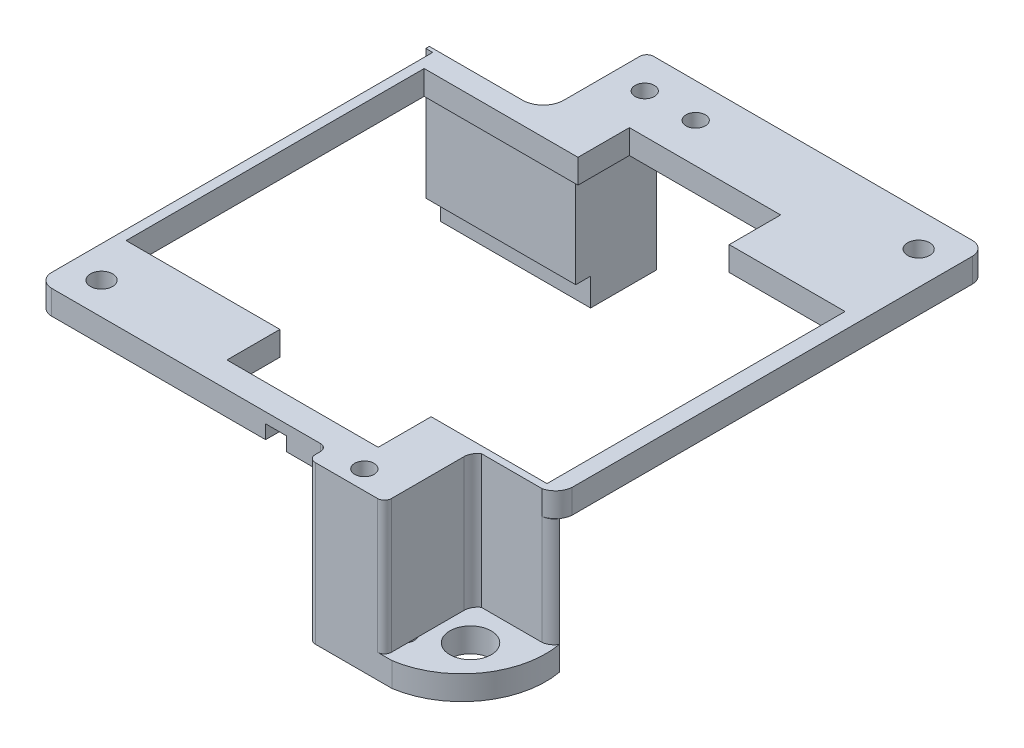
SolidWorks part; units mm, degrees
ref_plane "Спереди" through (0, 0, 0) normal (0, 0, 1) x (1, 0, 0)
ref_plane "Сверху" through (0, 0, 0) normal (0, 1, 0) x (1, 0, 0)
ref_plane "Справа" through (0, 0, 0) normal (1, 0, 0) x (0, 0, -1)
sketch "Sketch2" plane through (0, 3.6, 0) normal (0, -1, 0) x (1, 0, 0)
  line L22 (11.1116, -27.048) -> (11.1116, -19.6)
  line L23 (11.1116, -19.6) -> (27.9, -19.6)
  line L24 (27.9, -19.6) -> (27.9, 23.6)
  line L25 (27.9, 23.6) -> (11.1116, 23.6)
  line L26 (11.1116, 23.6) -> (11.1116, 31.2769)
  line L27 (11.1116, 31.2769) -> (1.5, 31.2769)
  line L28 (1.5, 31.2769) -> (1.5, 34.9854)
  line L29 (1.5, 34.9854) -> (6.4639, 34.9854)
  line L30 (-1.5, 31.2769) -> (-10.8084, 31.2769)
  line L31 (-10.8084, 31.2769) -> (-10.8084, 23.6)
  line L32 (-10.8084, 23.6) -> (-33.1, 23.6)
  line L33 (-33.5, -27.6627) -> (-33.5, -23.75)
  line L34 (-32.5, -22.75) -> (-22, -22.75)
  line L35 (-19, -25.75) -> (-19, -36.75)
  line L36 (-18, -37.75) -> (28.1923, -37.75)
  line L37 (30.1923, -35.7501) -> (30.1923, 22.25)
  line L38 (28.1923, 24.5898) -> (19.3848, 24.5898)
  line L39 (18.5, 26.25) -> (18.5, 36.75)
  line L40 (17.5, 37.75) -> (8.4639, 37.75)
  line L41 (7.4639, 36.75) -> (7.4639, 35.9854)
  line L42 (-1.5, 34.9854) -> (-32.5, 34.9854)
  line L43 (-34.5, 32.9854) -> (-34.5, -28.6627)
  line L44 (-33.1, 23.6) -> (-33.1, -19.6)
  line L45 (-33.1, -19.6) -> (-10.8084, -19.6)
  line L46 (-10.8084, -19.6) -> (-10.8084, -27.048)
  line L47 (-10.8084, -27.048) -> (11.1116, -27.048)
  line L48 (-1.5, 31.2769) -> (-1.5, 34.9854)
  circle A0 centre (-6.9188, -32.7663) radius 1.4
  circle A22 centre (25.4, -32.7663) radius 1.6
  circle A23 centre (-14.2971, -32.7663) radius 1.4
  circle A24 centre (-29.9119, 30.3479) radius 1.6
  circle A25 centre (12.8146, 34.9854) radius 1.4
  arc A33 (-34.5, -28.6627) -> (-33.5, -27.6627) centre (-34.5, -27.6627) ccw
  arc A34 (-32.5, -22.75) -> (-33.5, -23.75) centre (-32.5, -23.75) ccw
  arc A35 (-19, -25.75) -> (-22, -22.75) centre (-22, -25.75) ccw
  arc A36 (-19, -36.75) -> (-18, -37.75) centre (-18, -36.75) ccw
  arc A37 (28.1923, -37.75) -> (30.1923, -35.7501) centre (28.1923, -35.75) ccw
  arc A38 (30.1923, 22.25) -> (28.1923, 24.5898) centre (27.5559, 22.0212) ccw
  arc A39 (18.5, 26.25) -> (19.3848, 24.5898) centre (20.5, 26.25) ccw
  arc A40 (18.5, 36.75) -> (17.5, 37.75) centre (17.5, 36.75) ccw
  arc A41 (8.4639, 37.75) -> (7.4639, 36.75) centre (8.4639, 36.75) ccw
  arc A42 (6.4639, 34.9854) -> (7.4639, 35.9854) centre (6.4639, 35.9854) ccw
  arc A43 (-32.5, 34.9854) -> (-34.5, 32.9854) centre (-32.5, 32.9854) ccw
  point P57 (0, 0)
  point P58 (0, 0)
  point P59 (0, 0)
  dimension "D1" = 0
  dimension "D2" = 1.4
extrude "Boss-Extrude1" add sketch "Sketch2" along normal blind 3.5
sketch "Sketch3" plane through (0, 0.1, 0) normal (0, -1, 0) x (-1, 0, 0)
  line L0 (-7.4639, -33.9854) -> (-7.4639, -36.75)
  line L1 (-7.4639, -36.75) -> (-7.4639, -35.9854) construction
  line L2 (-8.4639, -37.75) -> (-17.5, -37.75)
  line L3 (-17.5, -37.75) -> (-8.4639, -37.75) construction
  line L4 (-11.1116, -24.25) -> (-11.1116, -23.6)
  line L5 (-18.5, -36.75) -> (-18.5, -26.25)
  line L6 (-18.5, -26.25) -> (-18.5, -36.75) construction
  line L7 (13.7749, 22.2395) -> (34.5, 22.2395)
  line L8 (-11.1116, -24.25) -> (-11.1116, -33.9854)
  line L9 (-11.1116, -33.9854) -> (-7.4639, -33.9854)
  line L10 (-11.1116, -23.6) -> (-29.6796, -23.6)
  line L12 (-28.1923, -24.5898) -> (-19.3848, -24.5898)
  line L13 (13.7749, 23.7464) -> (13.7749, 22.2395)
  line L14 (29.0773, 22.2395) -> (12.89, 22.2395) construction
  line L15 (34.5, 22.2395) -> (34.5, 23.75)
  line L16 (22, 22.75) -> (32.5, 22.75)
  line L19 (13.7749, 23.7464) -> (13.7749, 31.4673)
  line L20 (13.7749, 31.4673) -> (13.7749, 33.9534)
  line L22 (13.7749, 33.9534) -> (19, 33.9534)
  line L23 (19, 25.75) -> (19, 36.75) construction
  line L24 (19, 33.9534) -> (19, 25.75)
  line L26 (33.5, 27.6627) -> (33.5, 23.75) construction
  line L27 (34.5, -32.9854) -> (34.5, 28.6627) construction
  line L28 (34.5, 23.75) -> (34.5, 28.6627)
  line L30 (33.5, 27.6627) -> (33.5, 23.75)
  arc A0 (-8.4639, -37.75) -> (-7.4639, -36.75) centre (-8.4639, -36.75) ccw construction
  arc A1 (-7.4639, -36.75) -> (-8.4639, -37.75) centre (-8.4639, -36.75) cw
  arc A2 (-18.5, -36.75) -> (-17.5, -37.75) centre (-17.5, -36.75) ccw construction
  arc A3 (-18.5, -26.25) -> (-19.3848, -24.5898) centre (-20.5, -26.25) ccw construction
  arc A4 (-17.5, -37.75) -> (-18.5, -36.75) centre (-17.5, -36.75) cw
  arc A5 (-18.5, -26.25) -> (-19.3848, -24.5898) centre (-20.5, -26.25) ccw
  arc A6 (-30.1923, -22.25) -> (-28.1923, -24.5898) centre (-27.5559, -22.0212) ccw construction
  arc A7 (-29.6796, -23.6) -> (-28.1923, -24.5898) centre (-27.9446, -22.6052) ccw
  arc A8 (19.7672, 23.7464) -> (22, 22.75) centre (22, 25.75) ccw
  arc A9 (33.5, 23.75) -> (32.5, 22.75) centre (32.5, 23.75) cw
  circle A10 centre (-12.8146, -34.9854) radius 1.4
  circle A12 centre (14.2971, 32.7663) radius 1.4 construction
  arc A15 (19, 25.75) -> (22, 22.75) centre (22, 25.75) ccw construction
  arc A16 (19, 25.75) -> (19.7672, 23.7464) centre (22, 25.75) ccw
  arc A17 (32.5, 22.75) -> (33.5, 23.75) centre (32.5, 23.75) ccw construction
  arc A18 (34.5, 28.6627) -> (33.5, 27.6627) centre (34.5, 27.6627) ccw construction
  arc A19 (33.5, 27.6627) -> (34.5, 28.6627) centre (34.5, 27.6627) cw
  point P36 (-19.3848, -24.5898)
extrude "Boss-Extrude2" add sketch "Sketch3" along normal blind 15.8
sketch "Sketch4" plane through (0, -15.7, 0) normal (0, -1, 0) x (1, 0, 0)
  line L0 (11.1116, 23.6) -> (29.6796, 23.6)
  line L1 (-13.7749, -33.9534) -> (-13.7749, -22.2395) construction
  line L2 (-34.5, -22.2395) -> (-34.5, -28.6627) construction
  line L3 (19.5777, 37.75) -> (8.4639, 37.75)
  line L4 (-29.8443, -33.9534) -> (-13.7749, -33.9534)
  line L5 (7.4639, 36.75) -> (7.4639, 33.9854)
  line L6 (7.4639, 33.9854) -> (11.1116, 33.9854) construction
  line L7 (7.4639, 36.75) -> (7.4639, 33.9854) construction
  line L8 (7.4639, 33.9854) -> (11.1116, 33.9854)
  line L9 (11.1116, 33.9854) -> (11.1116, 23.6)
  line L10 (-13.7749, -22.2395) -> (-34.5, -22.2395)
  line L11 (-13.7749, -33.9534) -> (-13.7749, -22.2395) construction
  line L12 (-34.5, -22.2395) -> (-34.5, -28.6627) construction
  line L13 (-34.5, -22.2395) -> (-34.5, -28.6627)
  line L14 (-13.7749, -33.9534) -> (-13.7749, -22.2395)
  line L15 (11.1116, 23.6) -> (29.6796, 23.6) construction
  arc A0 (29.6796, 23.6) -> (19.5777, 37.75) centre (17.7408, 25.7577) ccw
  arc A1 (-34.5, -28.6627) -> (-29.8443, -33.9534) centre (-19.7885, -20.4106) ccw
  circle A2 centre (23.0406, 29.8242) radius 3
  circle A3 centre (17.1804, 33.65) radius 1.5
  arc A4 (8.4639, 37.75) -> (7.4639, 36.75) centre (8.4639, 36.75) ccw
  arc A5 (8.4639, 37.75) -> (7.4639, 36.75) centre (8.4639, 36.75) ccw
  circle A6 centre (-23.9566, -27.7968) radius 3
  circle A7 centre (-30.7077, -27.9532) radius 1.5
  arc A8 (29.6796, 23.6) -> (28.1923, 24.5898) centre (27.9446, 22.6052) ccw construction
  dimension "D1" = 0
extrude "Boss-Extrude3" add sketch "Sketch4" along normal blind 3.5
sketch "Sketch5" plane through (0, 3.6, 0) normal (0, 1, 0) x (1, 0, 0)
  line L1 (1.5, -34.9854) -> (-1.5, -34.9854)
  line L2 (1.5, -34.9854) -> (1.5, -31.2769)
  line L3 (1.5, -31.2769) -> (-1.5, -31.2769)
  line L4 (-1.5, -34.9854) -> (-1.5, -31.2769)
extrude "Boss-Extrude4" add sketch "Sketch5" against normal blind 1.5
sketch "Sketch6" plane through (0, 3.6, 0) normal (0, 1, 0) x (1, 0, 0)
  line L0 (-32.5, 22.75) -> (-22, 22.75) construction
  line L1 (-45.1552, 36.7564) -> (-29.9824, 36.7564)
  line L2 (-45.1552, 36.7564) -> (-45.1552, 22.75)
  line L3 (-45.1552, 22.75) -> (-29.9824, 22.75)
  line L4 (-29.9824, 36.7564) -> (-29.9824, 22.75)
sketch "Sketch7" plane through (0, -19.2, 0) normal (0, -1, 0) x (1, 0, 0)
  line L1 (-3.122, -12.248) -> (-38.6204, -12.248)
  line L2 (-3.122, -12.248) -> (-3.122, -24.3922)
  line L3 (-3.122, -24.3922) -> (-38.6204, -24.3922)
  line L4 (-38.6204, -12.248) -> (-38.6204, -24.3922)
extrude "Cut-Extrude2" cut sketch "Sketch7" against normal blind 4
sketch "Sketch8" plane through (-34.5, 0, 0) normal (-1, 0, 0) x (0, 0, 1)
  line L0 (-24.3922, -19.2) -> (-24.3922, -15.2)
  line L1 (-24.3922, -19.2) -> (-28.6627, -19.2)
  line L3 (-22.2395, 3.6) -> (-28.6627, 3.6)
  line L4 (-28.6627, -19.2) -> (-28.6627, 3.6)
  line L5 (-24.3922, -15.2) -> (-22.2395, -15.2)
  line L6 (-22.2395, -15.2) -> (-22.2395, 0.1)
  line L7 (-22.2395, 0.1) -> (-22.2395, 3.6)
  line L8 (32.9854, 3.6) -> (-28.6627, 3.6) construction
  point P15 (-22.3074, 3.6)
extrude "Boss-Extrude5" add sketch "Sketch8" along normal blind 1
extrude "Cut-Extrude3" cut sketch "Sketch6" against normal blind 15
chamfer "Chamfer1" distance 6 angle 45 1 edges at (-34, -11.4, -22.75)
